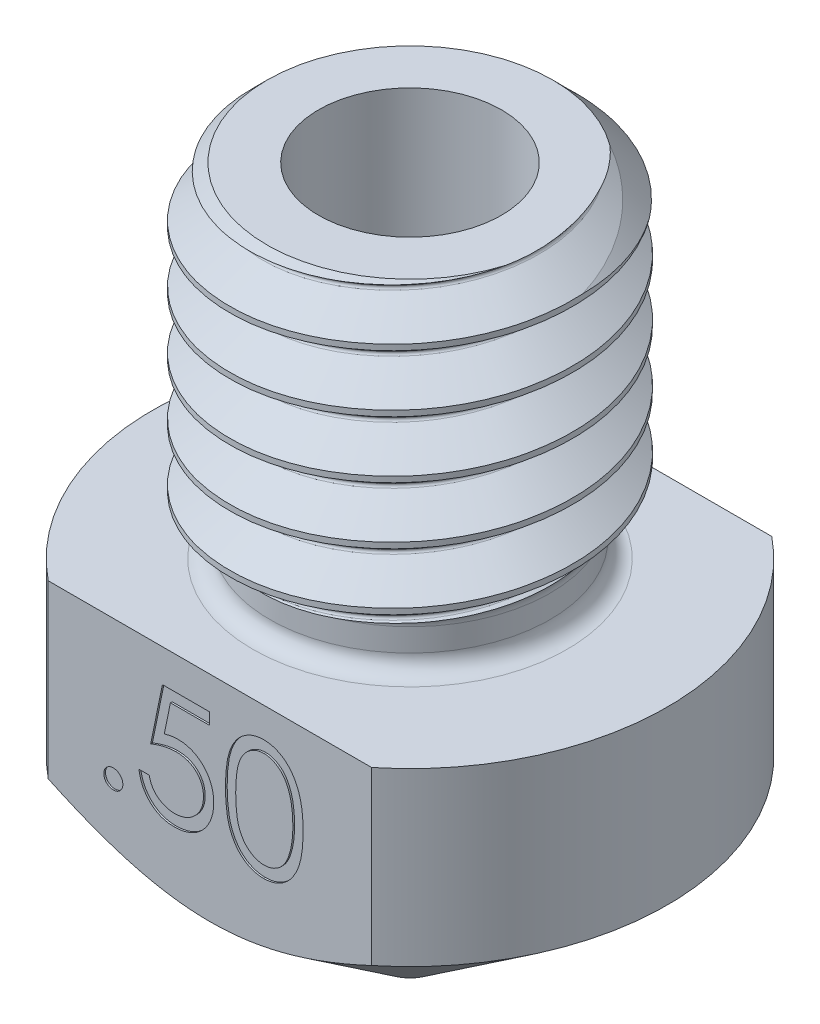
SolidWorks part; units mm, degrees
material "Brass"
ref_plane "Front Plane" through (0, 0, 0) normal (0, 0, 1) x (1, 0, 0)
ref_plane "Top Plane" through (0, 0, 0) normal (0, 1, 0) x (1, 0, 0)
ref_plane "Right Plane" through (0, 0, 0) normal (1, 0, 0) x (0, 0, -1)
sketch "Sketch1" plane through (0, 0, 0) normal (0, 0, 1) x (1, 0, 0)
  line L0 (0.25, 0) -> (0.25, 1.5)
  line L1 (0.25, 1.5) -> (1.6, 3.1089)
  line L2 (1.6, 3.1089) -> (1.6, 12)
  line L3 (1.6, 12) -> (2.5, 12)
  line L4 (3, 11.5) -> (3, 7)
  line L5 (3, 7) -> (2.75, 7)
  line L6 (2.45, 6.7) -> (2.45, 6.3)
  line L7 (2.75, 6) -> (4.5, 6)
  line L8 (4.5, 6) -> (4.5, 3)
  line L9 (0.25, 0) -> (0.5, 0)
  line L10 (0, 0) -> (0, 13.8999) construction
  line L11 (0.5, 0) -> (4.5, 3)
  line L12 (2.5, 12) -> (3, 11.5)
  arc A0 (2.75, 7) -> (2.45, 6.7) centre (2.75, 6.7) ccw
  arc A1 (2.45, 6.3) -> (2.75, 6) centre (2.75, 6.3) ccw
  point P5 (3, 12)
  dimension "D13" = 0.3
  dimension "D1" = 0.5
  dimension "D2" = 1
  dimension "D3" = 1.5
  dimension "D4" = 3
  dimension "D5" = 3
  dimension "D6" = 6
  dimension "D7" = 1
  dimension "D8" = 50
  dimension "D9" = 9
  dimension "D10" = 3.2
  dimension "D11" = 6
  dimension "D12" = 4.9
revolve "Revolve1" add sketch "Sketch1" angle 360 about L10
sketch "Sketch2" plane through (0, 6, 0) normal (0, 1, 0) x (1, 0, 0)
  line L0 (-6.9039, 3.5) -> (6.9039, -3.5) construction
  line L1 (-6.9039, 3.5) -> (6.9039, 3.5)
  line L2 (-6.9039, 3.5) -> (-6.9039, -3.5)
  line L3 (-6.9039, -3.5) -> (6.9039, -3.5)
  line L4 (6.9039, 3.5) -> (6.9039, -3.5)
  dimension "D1" = 7
extrude "Cut-Extrude1" cut sketch "Sketch2" against normal through all flip side to cut
ref_plane "Plane1" through (0, 6.9, 0) normal (0, 1, 0) x (-1, 0, 0)
sketch "Sketch4" plane through (0, 6.9, 0) normal (0, 1, 0) x (-1, 0, 0)
  circle A0 centre (0, 0) radius 3 construction
  circle A1 centre (0, 0) radius 3
curve "Helix/Spiral1" pitch 1 height 7 radius 3 centre (0, 6.9, 0) axis (0, 1, 0) start towards (0, 0, 1)
ref_plane "Plane2" through (-3, 6.9, 0) normal (0, 0.053, 0.9986) x (-1, 0, 0)
sketch "Sketch5" plane through (-3, 6.9, 0) normal (0, 0.053, 0.9986) x (-1, 0, 0)
  line L0 (0, 0.9) -> (-0.5789, 0.4908)
  line L1 (-0.5789, 0.4092) -> (0, 0)
  line L2 (0, 0) -> (0, 0.9)
  line L3 (-0.55, 0.45) -> (0, 0.45) construction
  arc A0 (-0.5789, 0.4908) -> (-0.5789, 0.4092) centre (-0.55, 0.45) ccw
  dimension "D1" = 0.05
  dimension "D3" = 0.6
  dimension "D2" = 0.9
sweep "Cut-Sweep1" cut profiles "Sketch5" path "Helix/Spiral1"
sketch "Sketch6" plane through (0, 0, 3.5) normal (0, 0, 1) x (1, 0, 0)
  text T0 ".50" font "Century Gothic" height 2
extrude "Cut-Extrude2" cut sketch "Sketch6" against normal blind 0.03
